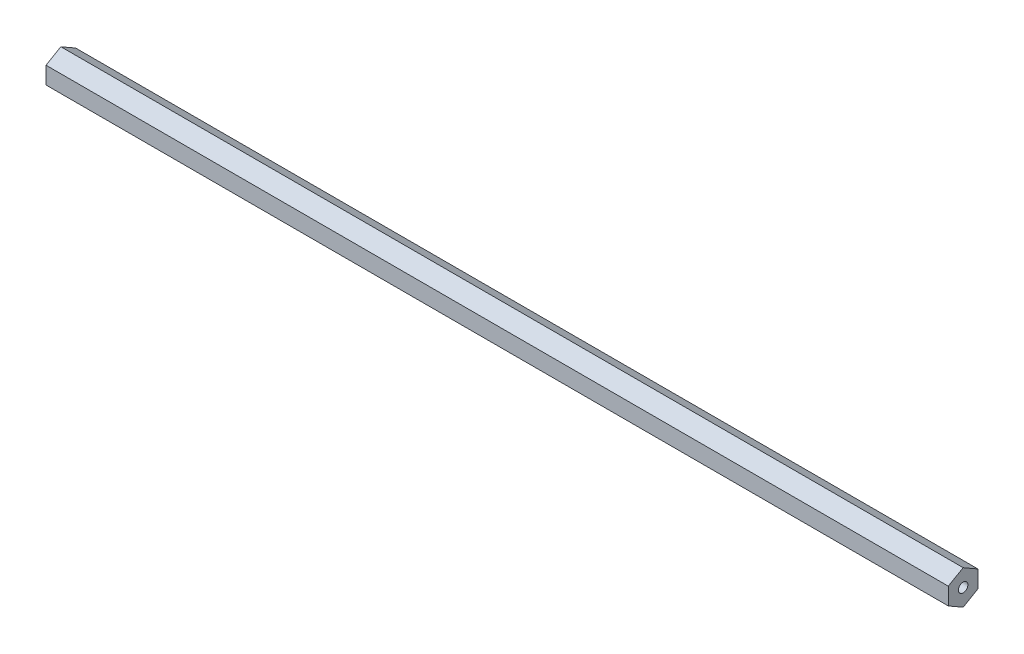
SolidWorks part; units mm, degrees
material "7075-T6 (SN)"
ref_plane "Front Plane" through (0, 0, 0) normal (0, 0, 1) x (1, 0, 0)
ref_plane "Top Plane" through (0, 0, 0) normal (0, 1, 0) x (1, 0, 0)
ref_plane "Right Plane" through (0, 0, 0) normal (1, 0, 0) x (0, 0, -1)
sketch "Sketch1" plane through (0, 0, 0) normal (1, 0, 0) x (0, 0, -1)
  line L1 (0, 7.3323) -> (-6.35, 3.6662)
  line L2 (-6.35, 3.6662) -> (-6.35, -3.6662)
  line L3 (-6.35, -3.6662) -> (0, -7.3323)
  line L4 (0, -7.3323) -> (6.35, -3.6662)
  line L5 (6.35, -3.6662) -> (6.35, 3.6662)
  line L6 (6.35, 3.6662) -> (0, 7.3323)
  circle A2 centre (0, 0) radius 6.35 construction
  dimension "D2" = 12.7
extrude "Boss-Extrude1" add sketch "Sketch1" along normal mid plane 385.7625 contours L5 L6 L1 L2 L3 L4 region at (0, 0, 0)
hole_wizard "#10-32 Tapped Hole1" positions "3DSketch1" profile "Sketch2" tap size "#10-32" standard "ANSI Inch"
sketch3d "3DSketch1"
  point P0 (192.8812, 0, 0)
  point P2 (-192.8812, 0, 0)
sketch "Sketch2" plane through (192.8812, 0, 0) normal (0, 1, 0) x (0, 0, -1)
  line L0 (0, 0) -> (0, 17.5608)
  line L1 (0, 17.5608) -> (2.0193, 16.3474)
  line L2 (2.0193, 16.3474) -> (2.0193, 0)
  line L5 (2.0193, 0) -> (0, 0)
  line L10 (0, 17.5608) -> (-2.0193, 16.3474) construction
  line L11 (0, -6.35) -> (0, 107.95) construction
  dimension "Tap Drill Dia." = 4.0386
  dimension "Tap Drill Depth" = 16.3474
  dimension "Drill Angle" = 118
cosmetic thread "Hole Thread1" parameters "D1"=13.97, "D2"=4.826
cosmetic thread "Hole Thread2" parameters "D1"=13.97, "D2"=4.826
